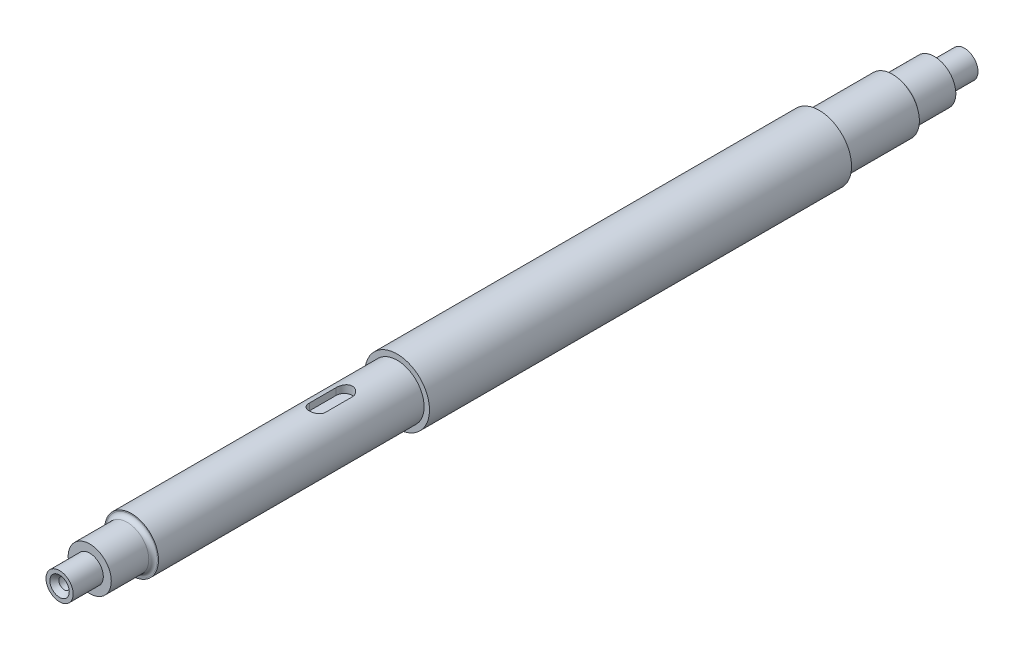
SolidWorks part; units mm, degrees
material "Alloy Steel"
ref_plane "Front Plane" through (0, 0, 0) normal (0, 0, 1) x (1, 0, 0)
ref_plane "Top Plane" through (0, 0, 0) normal (0, 1, 0) x (1, 0, 0)
ref_plane "Right Plane" through (0, 0, 0) normal (1, 0, 0) x (0, 0, -1)
sketch "Sketch1" plane through (0, 0, 0) normal (0, 0, 1) x (1, 0, 0)
  circle A0 centre (0, 0) radius 9.525
  dimension "D1" = 19.05
extrude "Boss-Extrude1" add sketch "Sketch1" along normal mid plane 279.4
ref_plane "Plane1" through (0, 0, 90.551) normal (0, 0, 1) x (1, 0, 0)
sketch "Sketch3" plane through (0, 0, 90.551) normal (0, 0, 1) x (1, 0, 0)
  circle A0 centre (0, 0) radius 7.9375
  circle A1 centre (0, 0) radius 9.525
  circle A2 centre (0, 0) radius 9.525
  dimension "D2" = 15.875
  dimension "D1" = 0
extrude "Cut-Extrude1" cut sketch "Sketch3" along normal up to next
mirror "Mirror1" about plane through (0, 0, 0) normal (0, 0, 1) of "Cut-Extrude1"
ref_plane "Plane2" through (0, 0, 124.46) normal (0, 0, 1) x (1, 0, 0)
sketch "Sketch4" plane through (0, 0, 124.46) normal (0, 0, 1) x (1, 0, 0)
  circle A0 centre (0, 0) radius 4
  circle A1 centre (0, 0) radius 7.9375
  circle A2 centre (0, 0) radius 7.9375
  dimension "D2" = 8
  dimension "D1" = 0
extrude "Cut-Extrude2" cut sketch "Sketch4" along normal up to next
mirror "Mirror2" about plane through (0, 0, 0) normal (0, 0, 1) of "Cut-Extrude2"
sketch "Sketch5" plane through (0, 0, 90.551) normal (0, 0, 1) x (1, 0, 0)
  circle A0 centre (0, 0) radius 9.525 construction
  circle A1 centre (0, 0) radius 9.525
  circle A3 centre (0, 0) radius 7.9375 construction
  circle A4 centre (0, 0) radius 7.9375
extrude "Cut-Extrude3" cut sketch "Sketch5" against normal blind 58.6105
ref_plane "Plane3" through (0, 7.9375, 0) normal (0, 1, 0) x (1, 0, 0)
sketch "Sketch6" plane through (0, 7.9375, 0) normal (0, 1, 0) x (1, 0, 0)
  line L0 (-9.525, -31.9405) -> (9.525, -31.9405) construction
  line L2 (-9.525, -31.9405) -> (9.525, -31.9405)
  line L3 (-7.9375, -124.46) -> (7.9375, -124.46) construction
  line L4 (0, -90.551) -> (0, -31.9405) construction
  line L8 (0, -57.3722) -> (0, -49.4347) construction
  line L9 (-2.3812, -57.3722) -> (-2.3813, -49.4348)
  line L10 (2.3813, -57.3722) -> (2.3812, -49.4347)
  line L11 (0, -47.0535) -> (-5.2744, -47.0535) construction
  line L12 (0, -59.7535) -> (-5.6689, -59.7535) construction
  line L13 (-7.9375, -124.46) -> (7.9375, -124.46) construction
  arc A0 (-2.3812, -57.3722) -> (2.3813, -57.3722) centre (0, -57.3722) ccw
  arc A1 (2.3812, -49.4347) -> (-2.3813, -49.4348) centre (0, -49.4347) ccw
  point P14 (0, -53.4035)
  dimension "D1" = 4.7625
  dimension "D2" = 12.7
  dimension "D3" = 37.1475
  dimension "D4" = 33.909
extrude "Cut-Extrude4" cut sketch "Sketch6" against normal blind 2.3812 contours L10 A1 L9 A0 region at (0, 7.9375, 53.4035)
sketch "Sketch7" plane through (0, 0, 124.46) normal (0, 0, 1) x (1, 0, 0)
  circle A0 centre (0, 0) radius 7.9375 construction
  circle A1 centre (0, 0) radius 7.9375
  circle A2 centre (0, 0) radius 6.35
  dimension "D1" = 12.7
extrude "Cut-Extrude5" cut sketch "Sketch7" against normal blind 12.319
fillet "Fillet1" radius 1.27 1 edges at (6.35, 0, 112.141)
sketch "Sketch8" plane through (0, 0, 139.7) normal (0, 0, 1) x (1, 0, 0)
  circle A0 centre (0, 0) radius 4 construction
  circle A1 centre (0, 0) radius 4
extrude "Cut-Extrude6" cut sketch "Sketch8" against normal blind 6.35
sketch "Sketch9" plane through (0, 0, 133.35) normal (0, 0, 1) x (1, 0, 0)
  circle A0 centre (0, 0) radius 4 construction
  circle A1 centre (0, 0) radius 4
  point P4 (0, 0)
hole_wizard "CSK for #4 Flat Head Machine Screw1" positions "3DSketch1" profile "Sketch10" countersink size "#4" standard "ANSI Inch"
sketch3d "3DSketch1"
  point P0 (0, 0, 133.35)
sketch "Sketch10" plane through (0, 0, 133.35) normal (1, 0, 0) x (0, -1, 0)
  line L0 (0, 0) -> (0, 7.3306)
  line L1 (0, 7.3306) -> (1.6319, 6.35)
  line L2 (1.6319, 6.35) -> (1.6319, 1.4098)
  line L3 (1.6319, 1.4098) -> (2.8575, 0)
  line L5 (2.8575, 0) -> (0, 0)
  line L6 (-1.6319, 1.4098) -> (-2.8575, 0) construction
  line L10 (0, 7.3306) -> (-1.6319, 6.35) construction
  line L11 (0, -6.35) -> (0, 107.95) construction
  dimension "Hole Dia." = 3.2639
  dimension "Hole Depth" = 6.35
  dimension "Near C'Sink Dia." = 5.715
  dimension "Near C'Sink Angle" = 82
  dimension "Drill Angle" = 118
mirror "Mirror3" about plane through (0, 0, 0) normal (0, 0, 1) of "CSK for #4 Flat Head Machine Screw1", "Fillet1", "Cut-Extrude5", "Cut-Extrude6"
sketch "Sketch11" plane through (0, 0, 31.9405) normal (0, 0, 1) x (1, 0, 0)
  circle A0 centre (0, 0) radius 7.9375 construction
  circle A1 centre (0, 0) radius 9.525 construction
  circle A2 centre (0, 0) radius 7.9375
  circle A3 centre (0, 0) radius 9.525
extrude "Boss-Extrude2" add sketch "Sketch11" along normal blind 1.905
